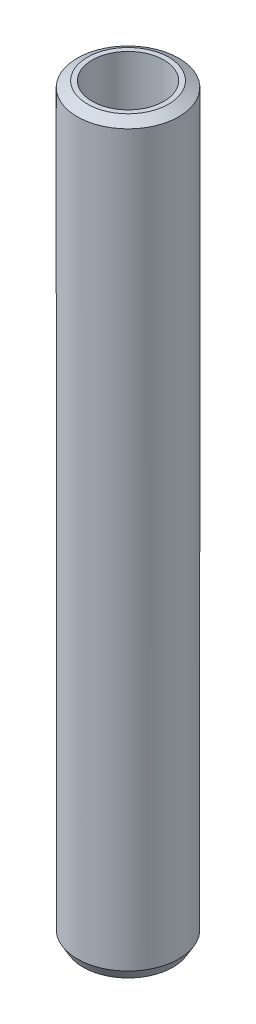
SolidWorks part; units mm, degrees
ref_plane "Front Plane" through (0, 0, 0) normal (0, 0, 1) x (1, 0, 0)
ref_plane "Top Plane" through (0, 0, 0) normal (0, 1, 0) x (1, 0, 0)
ref_plane "Right Plane" through (0, 0, 0) normal (1, 0, 0) x (0, 0, -1)
sketch "Sketch1" plane through (0, 0, 0) normal (0, 1, 0) x (1, 0, 0)
  circle A0 centre (0, 0) radius 20
  dimension "SHAFT_OD" = 40
extrude "Boss-Extrude1" add sketch "Sketch1" along normal blind 293.5413
sketch "Sketch2" plane through (0, 0, 0) normal (0, 1, 0) x (1, 0, 0)
  circle A0 centre (0, 0) radius 14.1167
  dimension "BORE_D" = 28.2334
extrude "Cut-Extrude1" cut sketch "Sketch2" along normal through all
chamfer "Chamfer1" distance 2.3085 angle 60 2 edges at (0, 293.5413, 20) (0, 0, 20) first distance on face at (0, 293.5413, 20) first distance on face at (0, 0, 14.1167)
